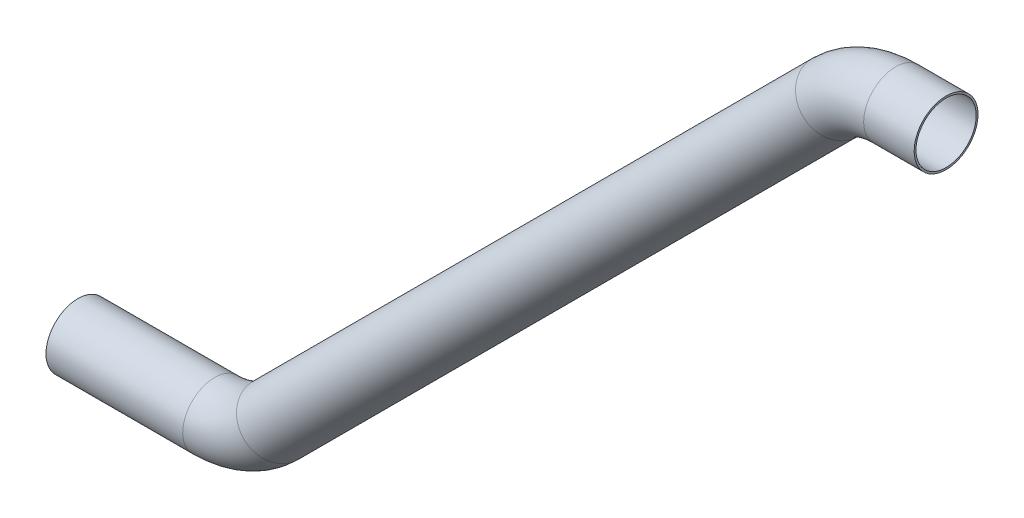
SolidWorks part; units mm, degrees
ref_plane "Front" through (0, 0, 0) normal (0, 0, 1) x (1, 0, 0)
ref_plane "Top" through (0, 0, 0) normal (0, 1, 0) x (1, 0, 0)
ref_plane "Right" through (0, 0, 0) normal (1, 0, 0) x (0, 0, -1)
sketch "Croquis1" plane through (0, 0, 0) normal (0, 0, 1) x (1, 0, 0)
  line L0 (0, 0) -> (237.868, 0)
  line L1 (343.934, 43.934) -> (1316.7262, 1016.7262)
  line L2 (1422.7922, 1060.6602) -> (1510.6602, 1060.6602)
  arc A0 (237.868, 0) -> (343.934, 43.934) centre (237.868, 150) ccw
  arc A1 (1316.7262, 1016.7262) -> (1422.7922, 1060.6602) centre (1422.7922, 910.6602) cw
  point P7 (300, 0)
  point P10 (1360.6602, 1060.6602)
  dimension "D5" = 150
  dimension "D1" = 45
  dimension "D2" = 1500
  dimension "D3" = 300
  dimension "D4" = 150
sweep "Barrer2" add path "Croquis1" circular profile diameter 111.125 parameters "D3"=111.125
shell "Vaciado1" thickness 3.175 removed face at (1510.6602, 1060.6602, 55.5625)
equation "\"Largo\"= 1500mm"
equation "\"D2@Croquis1\"=\"Largo\""
